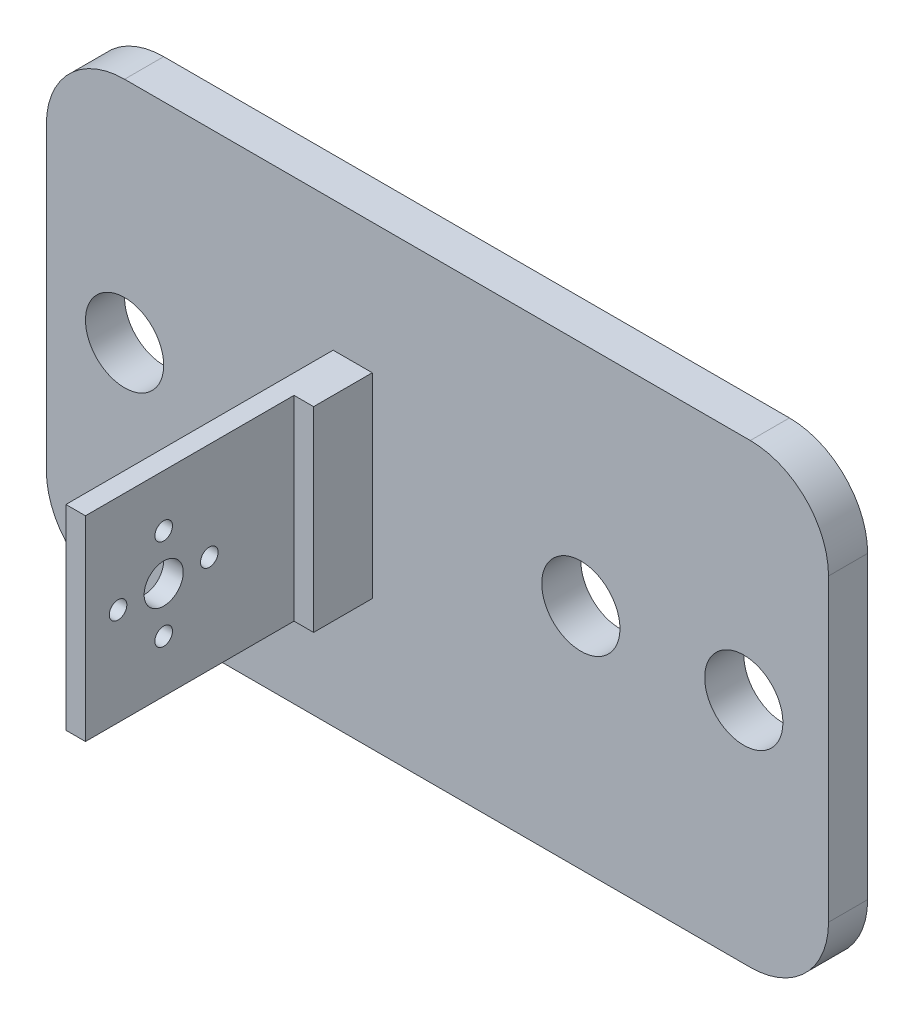
SolidWorks part; units mm, degrees
ref_plane "Front Plane" through (0, 0, 0) normal (0, 0, 1) x (1, 0, 0)
ref_plane "Top Plane" through (0, 0, 0) normal (0, 1, 0) x (1, 0, 0)
ref_plane "Right Plane" through (0, 0, 0) normal (1, 0, 0) x (0, 0, -1)
ref_plane "PZ_m35_000" through (0, 0, -35) normal (0, 0, 1) x (1, 0, 0)
sketch "S_box1" plane through (0, 0, -35) normal (0, 0, 1) x (1, 0, 0)
  line L0 (-62, -35) -> (58, -35)
  line L1 (58, -35) -> (58, 35)
  line L2 (58, 35) -> (-62, 35)
  line L3 (-62, 35) -> (-62, -35)
  dimension "P1" = 62
  dimension "P2" = 35
  dimension "P3" = 58
  dimension "P4" = 35
  dimension "P5" = 58
  dimension "P6" = 35
  dimension "P7" = 62
  dimension "P8" = 35
extrude "Boss_1" add sketch "S_box1" along normal blind 6
ref_plane "PZ_m29_500" through (0, 0, -29.5) normal (0, 0, 1) x (1, 0, 0)
sketch "S_box2" plane through (0, 0, -29.5) normal (0, 0, 1) x (1, 0, 0)
  line L0 (-18, -15) -> (-15, -15)
  line L1 (-15, -15) -> (-15, 15)
  line L2 (-15, 15) -> (-18, 15)
  line L3 (-18, 15) -> (-18, -15)
  dimension "P1" = 18
  dimension "P2" = 15
  dimension "P3" = 15
  dimension "P4" = 15
  dimension "P5" = 15
  dimension "P6" = 15
  dimension "P7" = 18
  dimension "P8" = 15
extrude "Boss_2" add sketch "S_box2" along normal blind 41.5
sketch "S_box3" plane through (0, 0, -29.5) normal (0, 0, 1) x (1, 0, 0)
  line L0 (-15.5, -15) -> (-12, -15)
  line L1 (-12, -15) -> (-12, 15)
  line L2 (-12, 15) -> (-15.5, 15)
  line L3 (-15.5, 15) -> (-15.5, -15)
  dimension "P1" = 15.5
  dimension "P2" = 15
  dimension "P3" = 12
  dimension "P4" = 15
  dimension "P5" = 12
  dimension "P6" = 15
  dimension "P7" = 15.5
  dimension "P8" = 15
extrude "Boss_3" add sketch "S_box3" along normal blind 9.5
ref_plane "PX_m18_100" through (-18.1, 0, 0) normal (1, 0, 0) x (0, 0, -1)
sketch "S_hole4" plane through (-18.1, 0, 0) normal (1, 0, 0) x (0, 0, -1)
  circle A0 centre (0, 0) radius 3
  dimension "D1_S_hole4" = 6
extrude "Hole_4" cut sketch "S_hole4" along normal blind 3.2
sketch "S_hole5" plane through (-18.1, 0, 0) normal (1, 0, 0) x (0, 0, -1)
  circle A0 centre (0, 7) radius 1.35
  dimension "D1_S_hole5" = 2.7
  dimension "P2" = 7
extrude "Hole_5" cut sketch "S_hole5" along normal blind 3.2
sketch "S_hole6" plane through (-18.1, 0, 0) normal (1, 0, 0) x (0, 0, -1)
  circle A0 centre (-7, 0) radius 1.35
  dimension "D1_S_hole6" = 2.7
  dimension "P2" = 7
extrude "Hole_6" cut sketch "S_hole6" along normal blind 3.2
sketch "S_hole7" plane through (-18.1, 0, 0) normal (1, 0, 0) x (0, 0, -1)
  circle A0 centre (0, -7) radius 1.35
  dimension "D1_S_hole7" = 2.7
  dimension "P2" = 7
extrude "Hole_7" cut sketch "S_hole7" along normal blind 3.2
sketch "S_hole8" plane through (-18.1, 0, 0) normal (1, 0, 0) x (0, 0, -1)
  circle A0 centre (7, 0) radius 1.35
  dimension "D1_S_hole8" = 2.7
  dimension "P2" = 7
extrude "Hole_8" cut sketch "S_hole8" along normal blind 3.2
ref_plane "PZ_m35_100" through (0, 0, -35.1) normal (0, 0, 1) x (1, 0, 0)
sketch "S_hole9" plane through (0, 0, -35.1) normal (0, 0, 1) x (1, 0, 0)
  circle A0 centre (-50, 0) radius 6
  dimension "D1_S_hole9" = 12
  dimension "P2" = 50
extrude "Hole_9" cut sketch "S_hole9" along normal blind 6.2
sketch "S_hole10" plane through (0, 0, -35.1) normal (0, 0, 1) x (1, 0, 0)
  circle A0 centre (-20, 0) radius 6
  dimension "D1_S_hole10" = 12
  dimension "P2" = 20
extrude "Hole_10" cut sketch "S_hole10" along normal blind 6.2
sketch "S_hole11" plane through (0, 0, -35.1) normal (0, 0, 1) x (1, 0, 0)
  circle A0 centre (20, 0) radius 6
  dimension "D1_S_hole11" = 12
  dimension "P2" = 20
extrude "Hole_11" cut sketch "S_hole11" along normal blind 6.2
sketch "S_hole12" plane through (0, 0, -35.1) normal (0, 0, 1) x (1, 0, 0)
  circle A0 centre (45, 0) radius 6
  dimension "D1_S_hole12" = 12
  dimension "P2" = 45
extrude "Hole_12" cut sketch "S_hole12" along normal blind 6.2
sketch "S_pcut13" plane through (0, 0, -35.1) normal (0, 0, 1) x (1, 0, 0)
  line L0 (58.6, 35.6) -> (46, 35.6)
  line L1 (46, 35.6) -> (46, 35)
  line L2 (58, 23) -> (58.6, 23)
  line L3 (58.6, 23) -> (58.6, 35.6)
  arc A0 (46, 35) -> (58, 23) centre (46.0001, 23.0001) cw
extrude "Cut_13" cut sketch "S_pcut13" along normal blind 6.2
sketch "S_pcut14" plane through (0, 0, -35.1) normal (0, 0, 1) x (1, 0, 0)
  line L0 (58.6, -35.6) -> (46, -35.6)
  line L1 (46, -35.6) -> (46, -35)
  line L2 (58, -23) -> (58.6, -23)
  line L3 (58.6, -23) -> (58.6, -35.6)
  arc A0 (46, -35) -> (58, -23) centre (46.0001, -23.0001) ccw
extrude "Cut_14" cut sketch "S_pcut14" along normal blind 6.2
sketch "S_pcut15" plane through (0, 0, -35.1) normal (0, 0, 1) x (1, 0, 0)
  line L0 (-62.6, 35.6) -> (-50, 35.6)
  line L1 (-50, 35.6) -> (-50, 35)
  line L2 (-62, 23) -> (-62.6, 23)
  line L3 (-62.6, 23) -> (-62.6, 35.6)
  arc A0 (-50, 35) -> (-62, 23) centre (-50.0001, 23.0001) ccw
extrude "Cut_15" cut sketch "S_pcut15" along normal blind 6.2
sketch "S_pcut16" plane through (0, 0, -35.1) normal (0, 0, 1) x (1, 0, 0)
  line L0 (-62.6, -35.6) -> (-50, -35.6)
  line L1 (-50, -35.6) -> (-50, -35)
  line L2 (-62, -23) -> (-62.6, -23)
  line L3 (-62.6, -23) -> (-62.6, -35.6)
  arc A0 (-50, -35) -> (-62, -23) centre (-50.0001, -23.0001) cw
extrude "Cut_16" cut sketch "S_pcut16" along normal blind 6.2
equation "\"plate_t\" = 3"
equation "\"clearance\" = 0.4"
